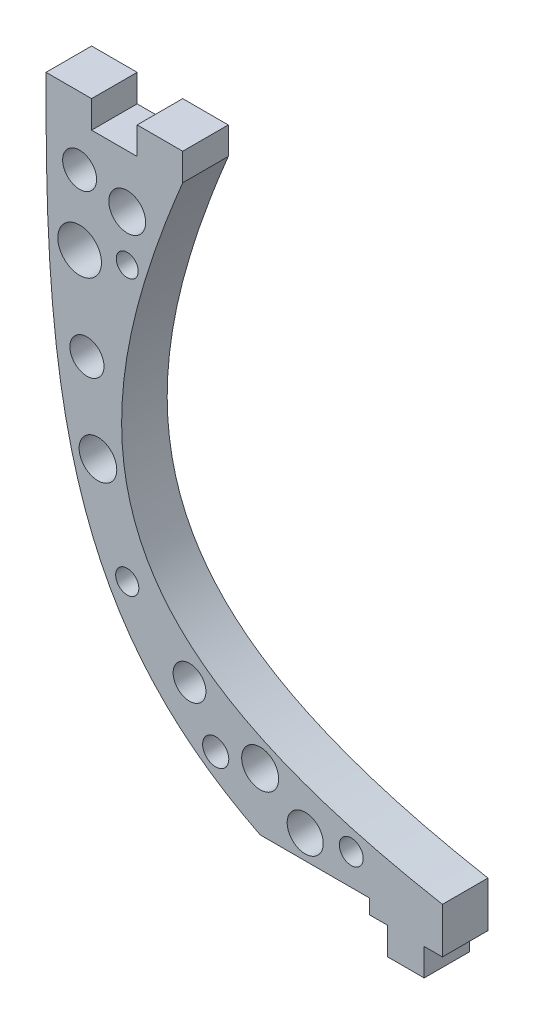
SolidWorks part; units mm, degrees
ref_plane "Plan de face" through (0, 0, 0) normal (0, 0, 1) x (1, 0, 0)
ref_plane "Plan de dessus" through (0, 0, 0) normal (0, 1, 0) x (1, 0, 0)
ref_plane "Plan de droite" through (0, 0, 0) normal (1, 0, 0) x (0, 0, -1)
sketch "Esquisse3" plane through (0, 0, 0) normal (0, 0, 1) x (1, 0, 0)
  line L0 (-7.5, 57.73) -> (-7.5, 0) construction
  line L1 (7.5, 57.73) -> (7.5, 17.682) construction
  line L2 (30, -4.6) -> (30, -1.6)
  line L3 (34, -4.6) -> (30, -4.6)
  line L4 (30, -1.6) -> (28, -1.6)
  line L5 (28, -1.6) -> (28, 0)
  line L6 (28, 0) -> (-7.5, 0) construction
  line L7 (7.5, 17.682) -> (36, 3.4) construction
  line L8 (34, -4.6) -> (34, -1.6)
  line L9 (34, -1.6) -> (36, -1.6)
  line L10 (36, -1.6) -> (36, 3.4)
  line L11 (28, 0) -> (16, 0)
  line L12 (16, 0) -> (-7.5, 11.7764) construction
  line L13 (-7.5, 11.7764) -> (-7.5, 57.73) construction
  line L15 (-7.5, 93.6282) -> (-7.5, 21.7981) construction
  line L16 (0.2936, 7.8708) -> (32.1661, -8.1012) construction
  circle A0 centre (-3.8151, 53.3093) radius 1.8639
  circle A1 centre (1.412, 51.9307) radius 2.0235
  circle A2 centre (-3.8151, 45.6697) radius 2.394
  circle A3 centre (1.412, 46.8759) radius 1.2063
  circle A4 centre (-3.0109, 35.9622) radius 1.8701
  circle A5 centre (-1.8047, 26.8291) radius 2.0679
  circle A6 centre (1.412, 16.777) radius 1.2715
  circle A7 centre (8.2475, 10.6309) radius 1.7991
  circle A8 centre (11.1195, 5.4612) radius 1.436
  circle A9 centre (16, 6.3228) radius 2.0318
  circle A10 centre (20.9418, 2.6466) radius 1.9807
  circle A11 centre (25.9966, 3.4) radius 1.3116
  spline S0 degree 3 poles (16, 0) (-3.9203, 9.9825) (-7.5, 27.8008) (-7.5, 57.73) knots 0 0 0 0 1 1 1 1
  spline S1 degree 3 poles (36, 3.4) (-1.2755, 10.2128) (-5.5671, 26.4267) (7.5, 57.73) knots 0 0 0 0 1 1 1 1
  line B0 (0, 57.73) -> (0, 44.4605) construction
  line B1 (0, 57.73) -> (2.5, 57.73)
  line B2 (2.5, 60.73) -> (7.5, 60.73)
  line B3 (7.5, 60.73) -> (7.5, 57.73)
  line B4 (2.5, 60.73) -> (2.5, 57.73)
  line B5 (0, 57.73) -> (-2.5, 57.73)
  line B6 (-2.5, 57.73) -> (-2.5, 60.73)
  line B7 (-2.5, 60.73) -> (-7.5, 60.73)
  line B8 (-7.5, 60.73) -> (-7.5, 57.73)
  dimension "D1" = 3
  dimension "D2" = 4
  dimension "D3" = 2
  dimension "D4" = 2
  dimension "D5" = 1.6
  dimension "D6" = 5
  dimension "D7" = 30
  dimension "D8" = 12
  dimension "D9" = 12
  dimension "D10" = 57.73
sketch_block_instance "Insert M3 plots ep 5mm-3"
sketch_block "Insert M3 plots ep 5mm" parameters "D1"=5, "D2"=5, "D3"=3
extrude "Boss.-Extru.1" add sketch "Esquisse3" along normal blind 5 contours B5 B6 B7 B8 L0 L1 B3 B2 B4 B1 region at (30.7849, -3.1, 0)
